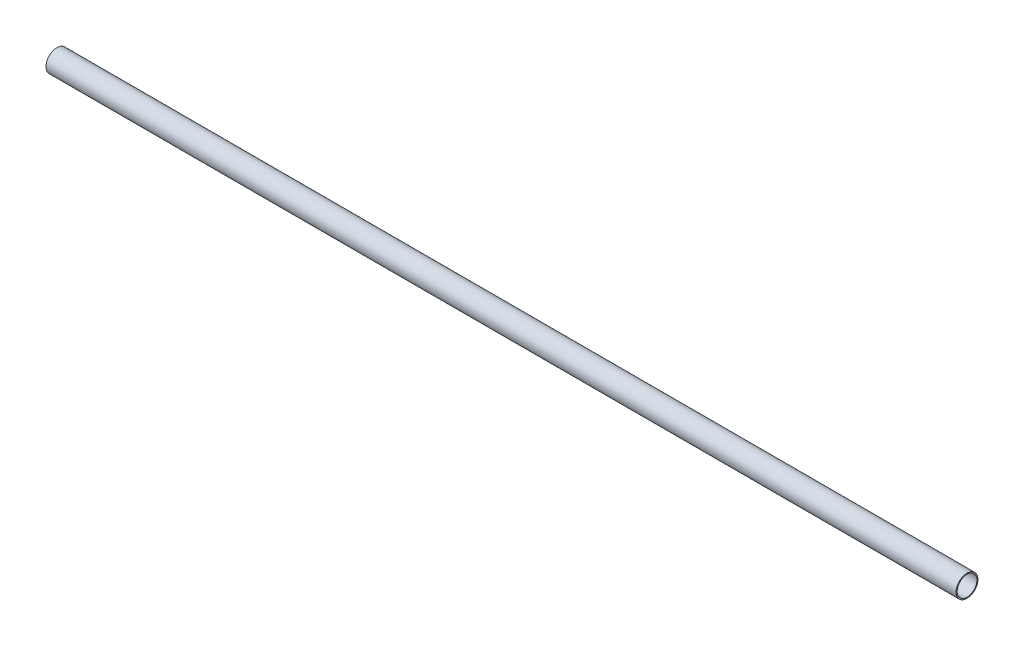
SolidWorks part; units mm, degrees
material "Thornel Mat VMA"
ref_plane "前视基准面" through (0, 0, 0) normal (0, 0, 1) x (1, 0, 0)
ref_plane "上视基准面" through (0, 0, 0) normal (0, 1, 0) x (1, 0, 0)
ref_plane "右视基准面" through (0, 0, 0) normal (1, 0, 0) x (0, 0, -1)
sketch "草图1" plane through (0, 0, 0) normal (1, 0, 0) x (0, 0, -1)
  circle A0 centre (0, 0) radius 5
  circle A1 centre (0, 0) radius 4.5
  dimension "D1" = 10
  dimension "D2" = 0.5
extrude "凸台-拉伸1" add sketch "草图1" along normal blind 415
